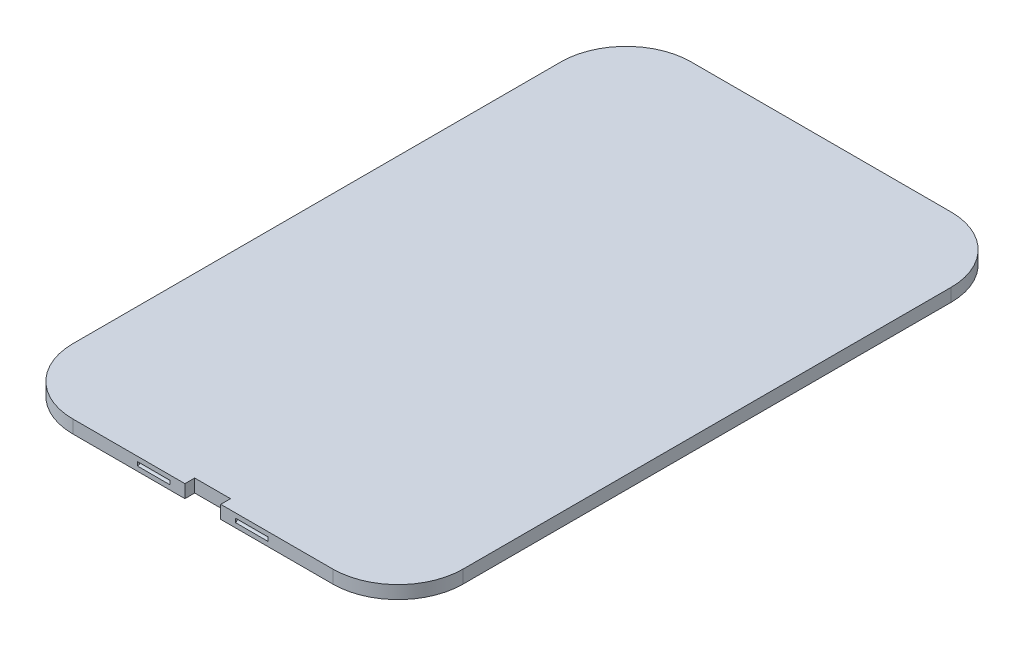
SolidWorks part; units mm, degrees
ref_plane "Front Plane" through (0, 0, 0) normal (0, 0, 1) x (1, 0, 0)
ref_plane "Top Plane" through (0, 0, 0) normal (0, 1, 0) x (1, 0, 0)
ref_plane "Right Plane" through (0, 0, 0) normal (1, 0, 0) x (0, 0, -1)
sketch "Sketch2" plane through (0, 0, 0) normal (0, 1, 0) x (1, 0, 0)
  line L0 (-25.3365, -60.2615) -> (25.3365, -60.2615)
  line L1 (-38.0365, -47.5615) -> (-38.0365, 47.5615)
  line L2 (38.0365, -47.5615) -> (38.0365, 47.5615)
  line L3 (-25.3365, 60.2615) -> (25.3365, 60.2615)
  line L4 (-38.0365, -60.2615) -> (38.0365, 60.2615) construction
  line L5 (38.0365, -60.2615) -> (-38.0365, 60.2615) construction
  arc A0 (-38.0365, 47.5615) -> (-25.3365, 60.2615) centre (-25.3365, 47.5615) cw
  arc A1 (38.0365, 47.5615) -> (25.3365, 60.2615) centre (25.3365, 47.5615) ccw
  arc A2 (25.3365, -60.2615) -> (38.0365, -47.5615) centre (25.3365, -47.5615) ccw
  arc A3 (-38.0365, -47.5615) -> (-25.3365, -60.2615) centre (-25.3365, -47.5615) ccw
  dimension "D3" = 12.7
  dimension "D4" = 12.7
  dimension "D1" = 120.523
  dimension "D2" = 76.073
extrude "top" add sketch "Sketch2" along normal blind 2.54
sketch "Sketch13" plane through (0, 0, -60.2615) normal (0, 0, -1) x (-1, 0, 0)
  line L0 (-25.3365, 0) -> (25.3365, 0) construction
  line L1 (-18.923, 0) -> (-6.477, 0)
  line L2 (-18.923, 0) -> (-18.923, 1.27)
  line L3 (-18.923, 1.27) -> (-6.477, 1.27)
  line L4 (-6.477, 0) -> (-6.477, 1.27)
  line L5 (0, 0) -> (0, 2.54) construction
  line L6 (-25.3365, 2.54) -> (25.3365, 2.54) construction
  line L7 (18.923, 0) -> (6.477, 0)
  line L8 (6.477, 0) -> (6.477, 1.27)
  line L9 (18.923, 1.27) -> (6.477, 1.27)
  line L10 (18.923, 0) -> (18.923, 1.27)
  dimension "D1" = 6.477
  dimension "D2" = 1.27
  dimension "D3" = 12.446
extrude "Body Tabs" add sketch "Sketch13" along normal blind 1.27 draft 7
sketch "Sketch14" plane through (0, 2.54, 0) normal (0, 1, 0) x (1, 0, 0)
  line L0 (0, -60.2615) -> (0, -56.9665) construction
  line L1 (-25.3365, -60.2615) -> (25.3365, -60.2615) construction
  line L3 (-3.4925, -60.2615) -> (3.4925, -60.2615)
  line L4 (-3.4925, -60.2615) -> (-3.4925, -58.3565)
  line L5 (-3.4925, -58.3565) -> (3.4925, -58.3565)
  line L6 (3.4925, -60.2615) -> (3.4925, -58.3565)
  dimension "D1" = 6.985
  dimension "D2" = 1.905
extrude "Flat Head Hole" cut sketch "Sketch14" against normal through all
sketch "Sketch15" plane through (0, 0, 60.2615) normal (0, 0, 1) x (1, 0, 0)
  line L0 (0, 0) -> (0, 2.54) construction
  line L1 (-12.7, 1.651) -> (-6.35, 1.651)
  line L2 (-12.7, 1.651) -> (-12.7, 0.889)
  line L3 (-12.7, 0.889) -> (-6.35, 0.889)
  line L4 (-6.35, 1.651) -> (-6.35, 0.889)
  line L5 (3.4925, 2.54) -> (-3.4925, 2.54) construction
  line L6 (0, 1.27) -> (-25.3365, 1.27) construction
  line L7 (-25.3365, 2.54) -> (-25.3365, 0) construction
  line L8 (-25.3365, 1.27) -> (25.3365, 1.27) construction
  line L9 (25.3365, 2.54) -> (25.3365, 0) construction
  line L10 (12.7, 1.651) -> (12.7, 0.889)
  line L11 (12.7, 0.889) -> (6.35, 0.889)
  line L12 (6.35, 1.651) -> (6.35, 0.889)
  line L13 (12.7, 1.651) -> (6.35, 1.651)
  point P16 (-6.35, 1.27)
  dimension "D1" = 0.762
  dimension "D2" = 6.35
  dimension "D3" = 6.35
extrude "Hold Grpoves" cut sketch "Sketch15" against normal blind 0.381
fillet "Hold Fillets" radius 0.381 4 edges at (9.525, 1.651, 59.8805) (9.525, 0.889, 59.8805) (-9.525, 0.889, 59.8805) (-9.525, 1.651, 59.8805)
